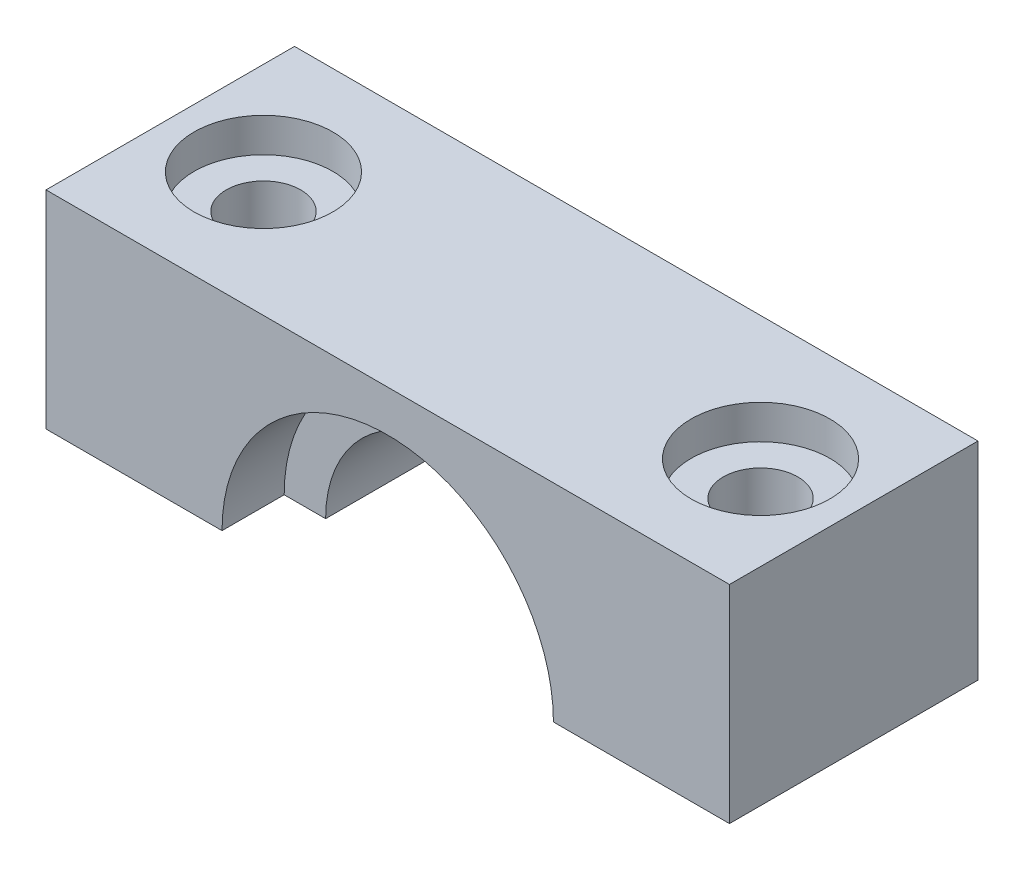
SolidWorks part; units mm, degrees
ref_plane "Front Plane" through (0, 0, 0) normal (0, 0, 1) x (1, 0, 0)
ref_plane "Top Plane" through (0, 0, 0) normal (0, 1, 0) x (1, 0, 0)
ref_plane "Right Plane" through (0, 0, 0) normal (1, 0, 0) x (0, 0, -1)
sketch "Sketch1" plane through (0, 0, 0) normal (0, 1, 0) x (1, 0, 0)
  line L0 (0, 6) -> (0, -6)
  line L1 (16.5, -6) -> (-16.5, -6)
  line L2 (16.5, -6) -> (16.5, 6)
  line L3 (16.5, 6) -> (-16.5, 6)
  line L4 (-16.5, -6) -> (-16.5, 6)
  line L5 (16.5, -6) -> (-16.5, 6) construction
  line L6 (16.5, 6) -> (-16.5, -6) construction
  line L8 (6, -3) -> (-6, -3)
  line L9 (6, -3) -> (6, 3)
  line L10 (6, 3) -> (-6, 3)
  line L11 (-6, -3) -> (-6, 3)
  line L12 (6, -3) -> (-6, 3) construction
  line L13 (6, 3) -> (-6, -3) construction
  line L14 (8, 6) -> (-8, 6)
  line L15 (8, 6) -> (8, 3)
  line L16 (8, 3) -> (-8, 3)
  line L17 (-8, 6) -> (-8, 3)
  line L18 (8, 6) -> (-8, 3) construction
  line L19 (8, 3) -> (-8, 6) construction
  line L20 (8, -6) -> (-8, -6)
  line L21 (8, -6) -> (8, -3)
  line L22 (8, -3) -> (-8, -3)
  line L23 (-8, -6) -> (-8, -3)
  line L24 (8, -6) -> (-8, -3) construction
  line L25 (8, -3) -> (-8, -6) construction
  point P0 (0, 0)
  point P8 (0, 0)
  point P13 (0, 4.5)
  point P18 (0, -4.5)
  dimension "D1" = 6
  dimension "D2" = 3
  dimension "D3" = 3
  dimension "D4" = 12
  dimension "D5" = 16
  dimension "D6" = 33
extrude "Boss-Extrude1" add sketch "Sketch1" along normal blind 10 contours L2 L3 L4 L1
revolve "Cut-Revolve1" cut sketch "Sketch1<4>" angle 360 about L0 region at (-4, 0, -4.5) region at (-3, 0, 0) region at (-4, 0, 4.5)
sketch "Sketch1<4>" plane through (0, 0, 0) normal (0, 1, 0) x (1, 0, 0) same geometry as "Sketch1"
sketch "Sketch2" plane through (0, 10, 0) normal (0, -1, 0) x (1, 0, 0)
  line L0 (16.5, 0) -> (-16.5, 0) construction
  line L1 (16.5, 6) -> (16.5, -6) construction
  line L2 (-16.5, 6) -> (-16.5, -6) construction
  line L3 (0, 0) -> (0, -9.6558) construction
  line L4 (-8, -3) -> (-8, -6) construction
  point P6 (12, 0)
  point P7 (-12, 0)
  dimension "D1" = 4
hole_wizard "CBORE for M3 SBHCS1" positions "3DSketch1" profile "Sketch3" counterbore size "M3" standard "ANSI Metric" end condition through all
sketch3d "3DSketch1"
  point P0 (-12, 10, 0)
  point P3 (12, 10, 0)
sketch "Sketch3" plane through (-12, 10, 0) normal (1, 0, 0) x (0, 0, 1)
  line L0 (0, 0) -> (0, 10)
  line L1 (0, 10) -> (1.8, 10)
  line L3 (1.8, 10) -> (1.8, 1.65)
  line L4 (1.8, 1.65) -> (3.35, 1.65)
  line L5 (3.35, 1.65) -> (3.35, 0)
  line L7 (3.35, 0) -> (0, 0)
  line L11 (0, -6.35) -> (0, 107.95) construction
  dimension "Thru Hole Dia." = 3.6
  dimension "Thru Hole Depth" = 10
  dimension "C'Bore Dia." = 6.7
  dimension "C'Bore Depth" = 1.65
